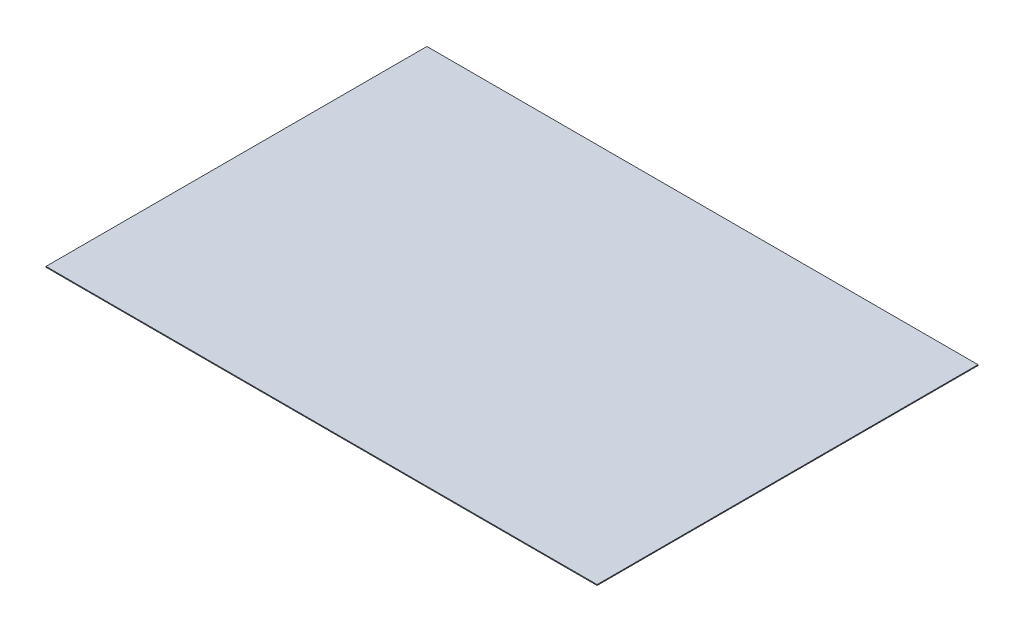
SolidWorks part; units mm, degrees
ref_plane "Front Plane" through (0, 0, 0) normal (0, 0, 1) x (1, 0, 0)
ref_plane "Top Plane" through (0, 0, 0) normal (0, 1, 0) x (1, 0, 0)
ref_plane "Right Plane" through (0, 0, 0) normal (1, 0, 0) x (0, 0, -1)
other "Configuration Table"
sketch "Sketch1" plane through (0, 0, 0) normal (0, 1, 0) x (1, 0, 0)
  line L1 (6475, -4475) -> (-6475, -4475)
  line L2 (6475, -4475) -> (6475, 4475)
  line L3 (6475, 4475) -> (-6475, 4475)
  line L4 (-6475, -4475) -> (-6475, 4475)
  line L5 (6475, -4475) -> (-6475, 4475) construction
  line L6 (6475, 4475) -> (-6475, -4475) construction
  point P0 (0, 0)
  dimension "D1" = 8950
  dimension "D2" = 12950
sheet metal parameters "Sheet-Metal1" thickness 20 parameters "D1"=0.7366
base flange "Base-Flange1" sketch "Sketch1" thickness 20 reverse thickness direction yes parameters "D1"=0.7366
flat pattern "Flat-Pattern1" [suppressed]
sketch "Bend-Lines1" plane through (0, 0, 0) normal (0, 1, 0) x (-1, 0, 0)
